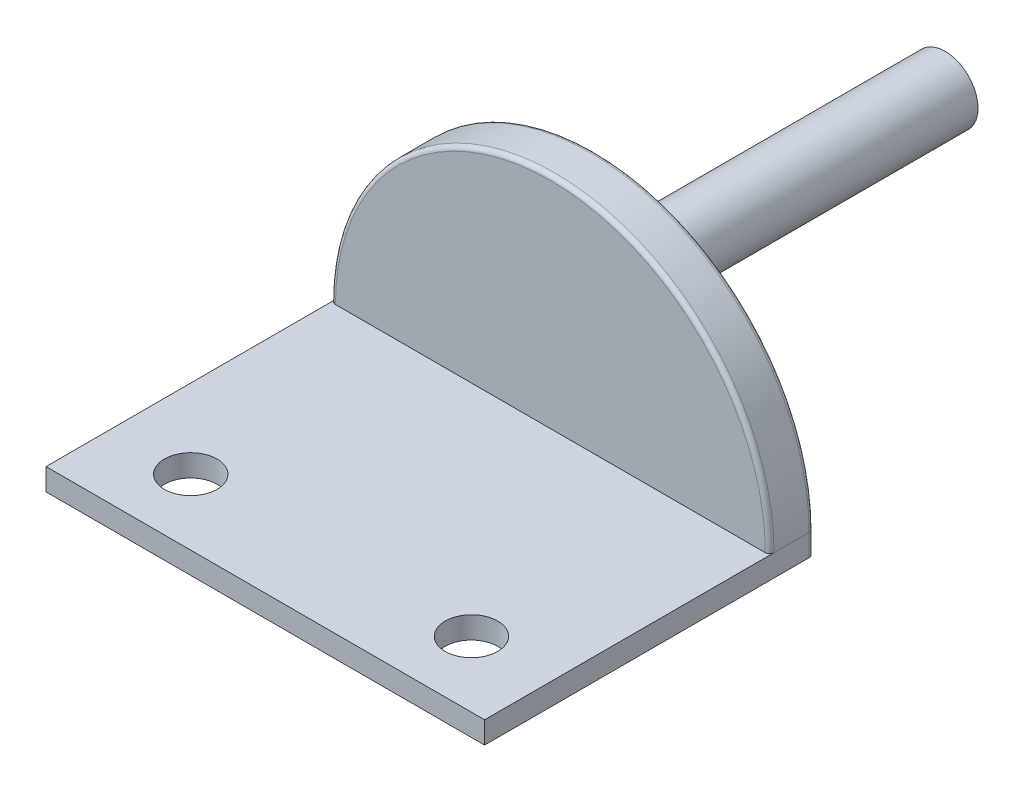
SolidWorks part; units mm, degrees
ref_plane "Front Plane" through (0, 0, 0) normal (0, 0, 1) x (1, 0, 0)
ref_plane "Top Plane" through (0, 0, 0) normal (0, 1, 0) x (1, 0, 0)
ref_plane "Right Plane" through (0, 0, 0) normal (1, 0, 0) x (0, 0, -1)
sketch "Sketch2" plane through (0, 0, 0) normal (0, 1, 0) x (1, 0, 0)
  line L1 (-50, 37.5) -> (50, 37.5)
  line L2 (-50, 37.5) -> (-50, -37.5)
  line L3 (-50, -37.5) -> (50, -37.5)
  line L4 (50, 37.5) -> (50, -37.5)
  line L5 (-50, 37.5) -> (50, -37.5) construction
  line L6 (-50, -37.5) -> (50, 37.5) construction
  circle A0 centre (-32, -22.5) radius 6
  circle A1 centre (32, -22.5) radius 6
  point P0 (0, 0)
  dimension "D3" = 18
  dimension "D4" = 18
  dimension "D5" = 12
  dimension "D6" = 12
  dimension "D7" = 15
  dimension "D8" = 15
  dimension "D1" = 100
  dimension "D2" = 75
extrude "Boss-Extrude1" add sketch "Sketch2" along normal blind 5
sketch "Sketch3" plane through (0, 5, 0) normal (0, 1, 0) x (1, 0, 0)
  line L0 (-50, 27.5) -> (50, 27.5)
  line L1 (-50, 37.5) -> (-50, -37.5) construction
  line L2 (50, -37.5) -> (50, 37.5) construction
  line L3 (50, 37.5) -> (-50, 37.5) construction
  line L4 (-50, 27.5) -> (-50, 37.5)
  line L5 (-50, 37.5) -> (50, 37.5)
  line L6 (50, 37.5) -> (50, 27.5)
  dimension "D1" = 10
extrude "Boss-Extrude2" add sketch "Sketch3" along normal blind 50
sketch "Sketch5" plane through (0, 0, -27.5) normal (0, 0, 1) x (1, 0, 0)
  arc A0 (-50, 5) -> (50, 5) centre (0, 5) cw
extrude "Cut-Extrude2" cut sketch "Sketch5" against normal through all and the other way through all
fillet "Fillet1" radius 1 3 edges at (50, 2.5, -37.5) (-50, 2.5, -37.5) (0, 55, -37.5)
fillet "Fillet2" radius 1 1 edges at (0, 55, -27.5)
sketch "Sketch6" plane through (0, 0, -27.5) normal (0, 0, 1) x (1, 0, 0)
  line L0 (0, 0) -> (0, 54) construction
  arc A0 (49, 5) -> (-49, 5) centre (0, 5) ccw construction
  circle A4 centre (0, 27) radius 7.5
  dimension "D1" = 15
extrude "Boss-Extrude3" add sketch "Sketch6" against normal blind 90
